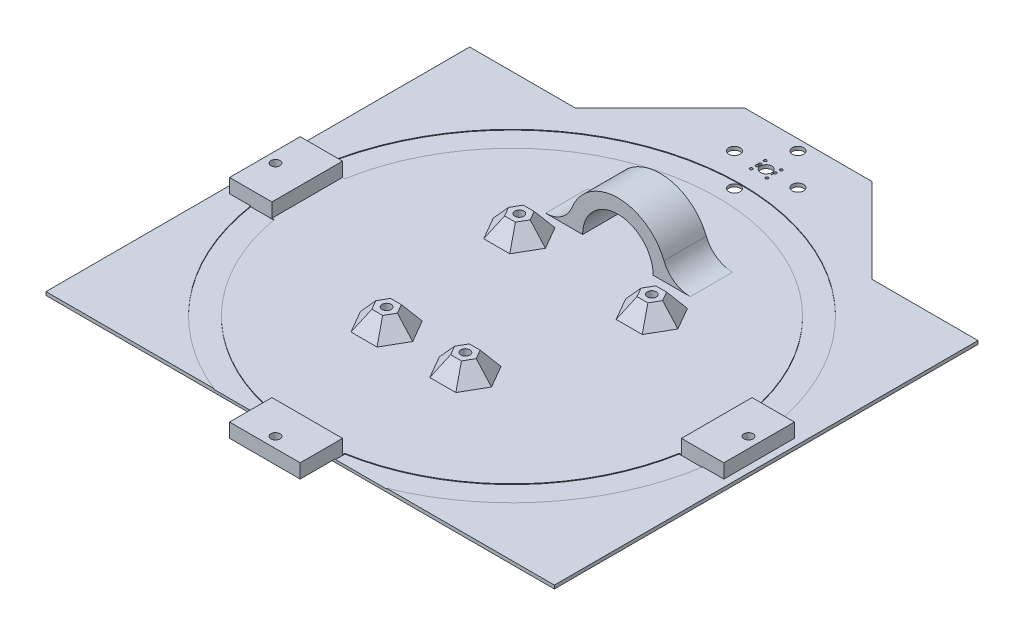
SolidWorks part; units mm, degrees
ref_plane "Front Plane" through (0, 0, 0) normal (0, 0, 1) x (1, 0, 0)
ref_plane "Top Plane" through (0, 0, 0) normal (0, 1, 0) x (1, 0, 0)
ref_plane "Right Plane" through (0, 0, 0) normal (1, 0, 0) x (0, 0, -1)
sketch "Sketch1" plane through (0, 0, 0) normal (0, 1, 0) x (1, 0, 0)
  line L0 (0, 75) -> (0, 105)
  line L1 (-90, -75) -> (90, -75)
  line L2 (-90, -75) -> (-90, 75)
  line L3 (-90, 75) -> (90, 75)
  line L4 (90, -75) -> (90, 75)
  line L5 (-90, -75) -> (90, 75) construction
  line L6 (-90, 75) -> (90, -75) construction
  line L7 (0, -55) -> (0, 55) construction
  line L8 (-22.5, 105) -> (22.5, 105)
  line L9 (22.5, 105) -> (52.5, 75)
  line L10 (-22.5, 105) -> (-52.5, 75)
  point P0 (0, 0)
  point P13 (0, 105)
  dimension "D1" = 150
  dimension "D2" = 180
  dimension "D3" = 30
  dimension "D4" = 45
  dimension "D5" = 105
extrude "Boss-Extrude1" add sketch "Sketch1" along normal blind 1.2 contours L1 L4 L3 L2 | L8 L10 L3 L0 | L9 L8 L0 L3
sketch "Sketch2" plane through (0, 1.2, 0) normal (0, 1, 0) x (1, 0, 0)
  line L0 (-24.1, 25.4) -> (-24.1, 26.7)
  line L1 (-24.1, -25.4) -> (24.1, -25.4)
  line L2 (-24.1, -25.4) -> (-24.1, 25.4)
  line L3 (-24.1, 25.4) -> (24.1, 25.4)
  line L4 (24.1, -25.4) -> (24.1, 25.4)
  line L5 (-24.1, -25.4) -> (24.1, 25.4) construction
  line L6 (-24.1, 25.4) -> (24.1, -25.4) construction
  line L7 (27.5641, 25.4) -> (25.8321, 28.4)
  line L8 (25.8321, 28.4) -> (22.3679, 28.4)
  line L9 (22.3679, 28.4) -> (20.6359, 25.4)
  line L10 (20.6359, 25.4) -> (22.3679, 22.4)
  line L11 (22.3679, 22.4) -> (25.8321, 22.4)
  line L12 (25.8321, 22.4) -> (27.5641, 25.4)
  line L13 (-24.1, -25.4) -> (-19, -25.4)
  line L14 (-20.6359, 26.7) -> (-22.3679, 29.7)
  line L15 (-22.3679, 29.7) -> (-25.8321, 29.7)
  line L16 (-25.8321, 29.7) -> (-27.5641, 26.7)
  line L17 (-27.5641, 26.7) -> (-25.8321, 23.7)
  line L18 (-25.8321, 23.7) -> (-22.3679, 23.7)
  line L19 (-22.3679, 23.7) -> (-20.6359, 26.7)
  line L20 (-19, -25.4) -> (8.9, -25.4)
  line L22 (-15.5359, -25.4) -> (-17.2679, -22.4)
  line L23 (-17.2679, -22.4) -> (-20.7321, -22.4)
  line L24 (-20.7321, -22.4) -> (-22.4641, -25.4)
  line L25 (-22.4641, -25.4) -> (-20.7321, -28.4)
  line L26 (-20.7321, -28.4) -> (-17.2679, -28.4)
  line L27 (-17.2679, -28.4) -> (-15.5359, -25.4)
  line L28 (12.3641, -25.4) -> (10.6321, -22.4)
  line L29 (10.6321, -22.4) -> (7.1679, -22.4)
  line L30 (7.1679, -22.4) -> (5.4359, -25.4)
  line L31 (5.4359, -25.4) -> (7.1679, -28.4)
  line L32 (7.1679, -28.4) -> (10.6321, -28.4)
  line L33 (10.6321, -28.4) -> (12.3641, -25.4)
  circle A0 centre (24.1, 25.4) radius 3 construction
  circle A1 centre (-24.1, 26.7) radius 3 construction
  circle A2 centre (-19, -25.4) radius 3 construction
  circle A3 centre (8.9, -25.4) radius 3 construction
  point P0 (0, 0)
  dimension "D1" = 48.2
  dimension "D2" = 50.8
  dimension "D3" = 1.3
  dimension "D4" = 5.1
  dimension "D5" = 27.9
extrude "Boss-Extrude2" add sketch "Sketch2" along normal blind 6 contours L11 L12 L7 L8 L9 L10 | L19 L14 L15 L16 L17 L18 | L32 L33 L28 L29 L30 L31 | L26 L27 L22 L23 L24 L25
chamfer "Chamfer1" distance 5 angle 52 48 edges at (6.3019, 1.2, 26.9) (6.3019, 7.2, 26.9) (6.3019, 1.2, 23.9) (6.3019, 7.2, 23.9) (8.9, 1.2, 22.4) (8.9, 7.2, 22.4) (11.4981, 1.2, 23.9) (11.4981, 7.2, 23.9) (11.4981, 1.2, 26.9) (11.4981, 7.2, 26.9) (8.9, 1.2, 28.4) (8.9, 7.2, 28.4) (-19, 1.2, 28.4) (-19, 7.2, 28.4) (-16.4019, 1.2, 26.9) (-16.4019, 7.2, 26.9) (-16.4019, 1.2, 23.9) (-16.4019, 7.2, 23.9) (-19, 1.2, 22.4) (-19, 7.2, 22.4) (-21.5981, 1.2, 23.9) (-21.5981, 7.2, 23.9) (-21.5981, 1.2, 26.9) (-21.5981, 7.2, 26.9) (21.5019, 1.2, -26.9) (21.5019, 7.2, -26.9) (21.5019, 1.2, -23.9) (21.5019, 7.2, -23.9) (24.1, 1.2, -22.4) (24.1, 7.2, -22.4) (26.6981, 1.2, -23.9) (26.6981, 7.2, -23.9) (26.6981, 1.2, -26.9) (26.6981, 7.2, -26.9) (24.1, 1.2, -28.4) (24.1, 7.2, -28.4) (-26.6981, 1.2, -28.2) (-26.6981, 7.2, -28.2) (-24.1, 1.2, -29.7) (-24.1, 7.2, -29.7) (-21.5019, 1.2, -28.2) (-21.5019, 7.2, -28.2) (-21.5019, 1.2, -25.2) (-21.5019, 7.2, -25.2) (-24.1, 1.2, -23.7) (-24.1, 7.2, -23.7) (-26.6981, 1.2, -25.2) (-26.6981, 7.2, -25.2)
sketch "Sketch3" plane through (0, 7.2, 0) normal (0, 1, 0) x (1, 0, 0)
  line L0 (6.9877, -22.0877) -> (10.8123, -28.7123) construction
  line L1 (-17.0877, -22.0877) -> (-20.9123, -28.7123) construction
  line L2 (-22.1877, 30.0123) -> (-26.0123, 23.3877) construction
  line L3 (26.0123, 28.7123) -> (22.1877, 22.0877) construction
  circle A0 centre (8.9, -25.4) radius 1.6
  circle A1 centre (-19, -25.4) radius 1.6
  circle A2 centre (-24.1, 26.7) radius 1.6
  circle A3 centre (24.1, 25.4) radius 1.6
extrude "Cut-Extrude1" cut sketch "Sketch3" against normal blind 5 contours A3 | A1 | A0 | A2
sketch "Sketch4" plane through (0, 1.2, 0) normal (0, 1, 0) x (1, 0, 0)
  line L0 (0, -10.285) -> (0, 10.285) construction
  line L1 (80, 0) -> (87.5, 0) construction
  line L2 (72.5, -12.5) -> (87.5, -12.5)
  line L3 (72.5, -12.5) -> (72.5, 12.5)
  line L4 (72.5, 12.5) -> (87.5, 12.5)
  line L5 (87.5, -12.5) -> (87.5, 12.5)
  line L6 (72.5, -12.5) -> (87.5, 12.5) construction
  line L7 (72.5, 12.5) -> (87.5, -12.5) construction
  line L8 (0, 0) -> (0, 4.4042)
  line L9 (0, -80) -> (0, -87.5) construction
  line L10 (-12.5, -87.5) -> (12.5, -87.5)
  line L11 (-12.5, -87.5) -> (-12.5, -72.5)
  line L12 (-12.5, -72.5) -> (12.5, -72.5)
  line L13 (12.5, -87.5) -> (12.5, -72.5)
  line L14 (-12.5, -87.5) -> (12.5, -72.5) construction
  line L15 (-12.5, -72.5) -> (12.5, -87.5) construction
  line L16 (-72.5, 12.5) -> (-87.5, 12.5)
  line L17 (-87.5, -12.5) -> (-87.5, 12.5)
  line L18 (-72.5, -12.5) -> (-87.5, -12.5)
  line L19 (-72.5, -12.5) -> (-72.5, 12.5)
  circle A0 centre (83.75, 0) radius 1.6
  circle A1 centre (-83.75, 0) radius 1.6
  circle A2 centre (0, -83.75) radius 1.6
  ellipse E0 centre (0, 0) end of major axis (0, 80) minor radius 80
  point P7 (80, 0)
  point P21 (0, -80)
  dimension "D3" = 15
  dimension "D1" = 15
  dimension "D2" = 25
  dimension "D4" = 25
extrude "Boss-Extrude3" add sketch "Sketch4" along normal blind 5 contours E0 L16 L17 L18 A1 | L16 E0 L18 L19 | L3 L4 L5 L2 | L12 L13 L10 L11 | A2 | A0
sketch "Sketch5" plane through (0, 1.2, 0) normal (0, 1, 0) x (1, 0, 0)
  line L0 (-80, 12.5) -> (-71.6819, 12.5)
  line L1 (-72.5, 12.5) -> (-87.5, 12.5) construction
  line L2 (-71.6819, -12.5) -> (-80, -12.5)
  line L3 (-72.5, -12.5) -> (-87.5, -12.5) construction
  line L4 (4.8047, -72.6048) -> (-12.5, -73.75)
  line L5 (-12.5, -75) -> (-12.5, -72.5) construction
  line L6 (12.5, -80) -> (12.5, -71.6819)
  line L7 (12.5, -87.5) -> (12.5, -72.5) construction
  line L8 (12.5, -75) -> (12.5, -72.5) construction
  line L9 (80, -12.5) -> (71.6819, -12.5)
  line L10 (72.5, -12.5) -> (87.5, -12.5) construction
  line L11 (71.6819, 12.5) -> (80, 12.5)
  line L12 (72.5, 12.5) -> (87.5, 12.5) construction
  circle A0 centre (0, 0) radius 72.7636
  circle A1 centre (0, 0) radius 81
  line M35 (-72.5, -12.5) -> (-87.5, -12.5)
  line M37 (-87.5, 12.5) -> (-72.5, 12.5)
  line M40 (87.5, -12.5) -> (72.5, -12.5)
  line M42 (72.5, 12.5) -> (87.5, 12.5)
  line M43 (-12.5, -75) -> (-12.5, -72.5)
  line M45 (12.5, -72.5) -> (12.5, -75)
extrude "Cut-Extrude2" cut sketch "Sketch5" against normal blind 0.25 contours A1 A0 M42 M37 | A1 A0 M35 M43 | A1 A0 M45 M40
ref_plane "Plane1" through (0, 0, -45) normal (0, 0, -1) x (-1, 0, 0)
sketch "Sketch6" plane through (0, 0, -45) normal (0, 0, -1) x (-1, 0, 0)
  line L0 (22.5, 1.2) -> (-22.5, 1.2) construction
  line L1 (-12.5, 1.2) -> (12.5, 1.2)
  line L2 (-12.5, 1.2) -> (-17.5, 1.2)
  line L3 (-17.5, 1.2) -> (17.5, 1.2)
  circle A0 centre (0, 1.2) radius 12.5
  circle A1 centre (0, 1.2) radius 17.5
extrude "Boss-Extrude4" add sketch "Sketch6" along normal blind 7.5 and the other way blind 7.5 contours A1 A0
fillet "Fillet1" radius 10 2 edges at (-17.5, 1.2, -45) (17.5, 1.2, -45)
sketch "Sketch7" plane through (0, 0, 0) normal (0, -1, 0) x (1, 0, 0)
  line L0 (-52.5, -75) -> (52.5, -75)
  line L1 (0, -75) -> (0, -105) construction
  line L2 (-22.5, -105) -> (22.5, -105) construction
  line L3 (13.75, -90) -> (11.25, -90)
  line L4 (-2.5, -103.75) -> (2.5, -103.75)
  line L5 (-2.5, -103.75) -> (-2.5, -76.25)
  line L6 (-2.5, -76.25) -> (2.5, -76.25)
  line L7 (2.5, -103.75) -> (2.5, -76.25)
  line L8 (-2.5, -103.75) -> (2.5, -76.25) construction
  line L9 (-2.5, -76.25) -> (2.5, -103.75) construction
  line L10 (-13.75, -92.5) -> (13.75, -92.5)
  line L11 (-13.75, -92.5) -> (-13.75, -87.5)
  line L12 (-13.75, -87.5) -> (13.75, -87.5)
  line L13 (13.75, -92.5) -> (13.75, -87.5)
  line L14 (-13.75, -92.5) -> (13.75, -87.5) construction
  line L15 (-13.75, -87.5) -> (13.75, -92.5) construction
  line L16 (0, -90) -> (0, -144.2113)
  line L17 (0, -90) -> (4.8692, -90)
  line L18 (2.5, -87.5) -> (2.8427, -92.4882)
  circle A0 centre (11.25, -90) radius 2
  circle A1 centre (-11.25, -90) radius 2
  circle A2 centre (0, -78.75) radius 2
  circle A3 centre (0, -101.25) radius 2
  circle A4 centre (0, -90) radius 2
  circle A5 centre (2.7056, -90.4929) radius 0.5
  circle A6 centre (2.8427, -92.4882) radius 0.5
  circle A7 centre (2.8427, -87.5118) radius 0.5
  circle A8 centre (2.7056, -89.5071) radius 0.5
  circle A9 centre (-2.8427, -87.5118) radius 0.5
  circle A10 centre (-2.7056, -89.5071) radius 0.5
  circle A11 centre (-2.8427, -92.4882) radius 0.5
  circle A12 centre (-2.7056, -90.4929) radius 0.5
  point P8 (0, -90)
  point P13 (0, -90)
  dimension "D4" = 2.5
  dimension "D5" = 2.5
  dimension "D6" = 5
  dimension "D7" = 2
  dimension "D1" = 27.5
  dimension "D2" = 27.5
  dimension "D3" = 2.5
  dimension "D8" = 5
  dimension "D9" = 5
extrude "Cut-Extrude3" cut sketch "Sketch7" against normal up to surface (1.2 mm away)
